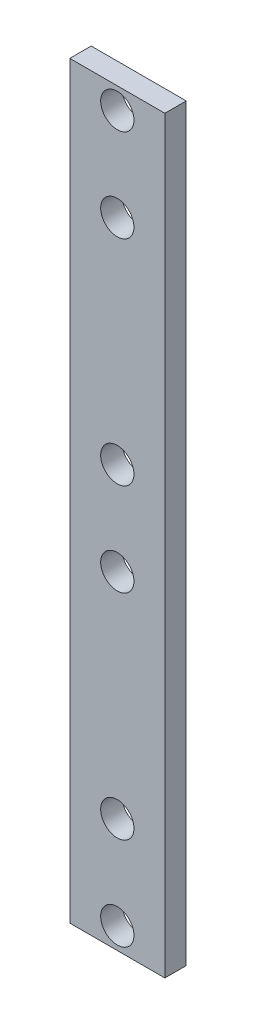
SolidWorks part; units mm, degrees
ref_plane "Front Plane" through (0, 0, 0) normal (0, 0, 1) x (1, 0, 0)
ref_plane "Top Plane" through (0, 0, 0) normal (0, 1, 0) x (1, 0, 0)
ref_plane "Right Plane" through (0, 0, 0) normal (1, 0, 0) x (0, 0, -1)
sketch "Sketch1" plane through (0, 0, 0) normal (0, 0, 1) x (1, 0, 0)
  line L6 (36.342, -76.5) -> (16.342, -76.5)
  line L7 (36.342, -76.5) -> (36.342, 81)
  line L8 (36.342, 81) -> (16.342, 81)
  line L9 (16.342, -76.5) -> (16.342, 81)
extrude "Boss-Extrude1" add sketch "Sketch1" along normal blind 4.5
sketch "Sketch2" plane through (0, 0, 4.5) normal (0, 0, 1) x (1, 0, 0)
  circle A0 centre (26.342, -72) radius 3.5
  circle A1 centre (26.342, -52.5) radius 3.5
  circle A2 centre (26.342, -7.5) radius 3.5
  circle A3 centre (26.342, 12) radius 3.5
  circle A4 centre (26.342, 57) radius 3.5
  circle A5 centre (26.342, 76.5) radius 3.5
  circle A6 centre (26.342, -72) radius 3.5 construction
  circle A7 centre (26.342, -52.5) radius 3.5 construction
  circle A8 centre (26.342, -7.5) radius 3.5 construction
  circle A9 centre (26.342, 12) radius 3.5 construction
  circle A10 centre (26.342, 57) radius 3.5 construction
  circle A11 centre (26.342, 76.5) radius 3.5 construction
extrude "Cut-Extrude1" cut sketch "Sketch2" against normal blind 4.5 contours A0 | A1 | A2 | A3 | A4 | A5
